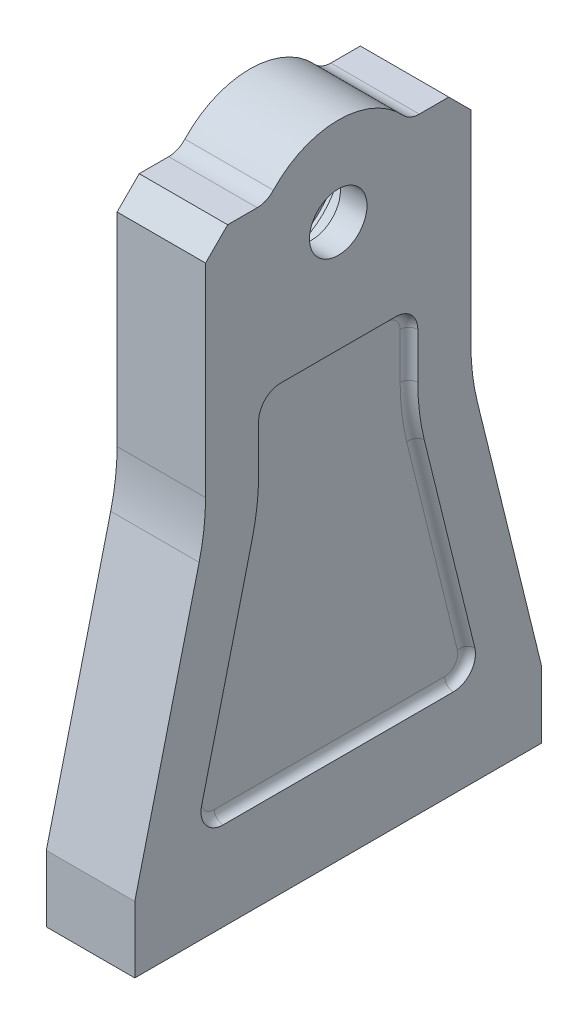
SolidWorks part; units mm, degrees
ref_plane "Front Plane" through (0, 0, 0) normal (0, 0, 1) x (1, 0, 0)
ref_plane "Top Plane" through (0, 0, 0) normal (0, 1, 0) x (1, 0, 0)
ref_plane "Right Plane" through (0, 0, 0) normal (1, 0, 0) x (0, 0, -1)
sketch "Sketch1" plane through (0, 0, 0) normal (1, 0, 0) x (0, 0, -1)
  line L0 (0, 133.7945) -> (0, -11.2055) construction
  line L1 (-46, -11.2055) -> (46, -11.2055)
  line L2 (-46, -11.2055) -> (-46, 3.7945)
  line L3 (-46, 3.7945) -> (-30, 68.7945)
  line L4 (-30, 68.7945) -> (-30, 120.7945)
  line L5 (-25, 125.7945) -> (-18.3303, 125.7945)
  line L6 (25, 125.7945) -> (18.3303, 125.7945)
  line L7 (30, 68.7945) -> (30, 120.7945)
  line L8 (46, 3.7945) -> (30, 68.7945)
  line L9 (46, -11.2055) -> (46, 3.7945)
  line L10 (-30, 120.7945) -> (-25, 125.7945)
  line L11 (30, 120.7945) -> (25, 125.7945)
  circle A0 centre (0, 113.7945) radius 6.5
  arc A1 (14.6642, 127.3945) -> (-14.6642, 127.3945) centre (0, 113.7945) ccw
  arc A2 (-18.3303, 125.7945) -> (-14.6642, 127.3945) centre (-18.3303, 130.7945) ccw
  arc A3 (18.3303, 125.7945) -> (14.6642, 127.3945) centre (18.3303, 130.7945) cw
  point P5 (0, -11.2055)
  point P9 (-30, 125.7945)
  point P13 (30, 125.7945)
  dimension "D7" = 13
  dimension "D8" = 40
  dimension "D9" = 5
  dimension "D1" = 92
  dimension "D2" = 30
  dimension "D3" = 15
  dimension "D4" = 65
  dimension "D5" = 12
  dimension "D6" = 125
extrude "Boss-Extrude1" add sketch "Sketch1" along normal mid plane 20
sketch "Sketch2" plane through (10, 0, 0) normal (1, 0, 0) x (0, 0, -1)
  line L28 (13, 88.7945) -> (-13, 88.7945)
  line L29 (-46, -11.2055) -> (46, -11.2055) construction
  line L30 (-26.031, 8.7945) -> (26.031, 8.7945)
  line L35 (-18, 120.7945) -> (-18, 67.3393)
  line L36 (18, 67.3393) -> (18, 120.7945)
  line L37 (34, 2.3393) -> (18, 67.3393)
  line L38 (34, 0.7945) -> (34, 2.3393)
  line L39 (-34, 0.7945) -> (34, 0.7945)
  line L40 (-34, 2.3393) -> (-34, 0.7945)
  line L41 (-18, 67.3393) -> (-34, 2.3393)
  line L42 (-18, 83.7945) -> (-18, 73.4026)
  line L43 (18, 73.4026) -> (18, 83.7945)
  line L44 (30.8861, 14.9896) -> (19.4493, 61.4517)
  line L48 (-19.4493, 61.4517) -> (-30.8861, 14.9896)
  arc A0 (-26.031, 8.7945) -> (-30.8861, 14.9896) centre (-26.031, 13.7945) cw
  arc A1 (26.031, 8.7945) -> (30.8861, 14.9896) centre (26.031, 13.7945) ccw
  arc A2 (13, 88.7945) -> (18, 83.7945) centre (13, 83.7945) cw
  arc A3 (-13, 88.7945) -> (-18, 83.7945) centre (-13, 83.7945) ccw
  arc A4 (18, 73.4026) -> (19.4493, 61.4517) centre (68, 73.4026) ccw
  arc A5 (-18, 73.4026) -> (-19.4493, 61.4517) centre (-68, 73.4026) cw
  dimension "D4" = 5
  dimension "D5" = 50
  dimension "D2" = 100
  dimension "D3" = 20
  dimension "D1" = 12
extrude "Cut-Extrude1" cut sketch "Sketch2" against normal mid plane 4
fillet "Fillet1" radius 2 12 edges at (8, 38.2206, 25.1677) (8, 67.3834, 18.3636) (8, 78.5986, 18) (8, 87.33, 16.5355) (8, 88.7945, 0) (8, 87.33, -16.5355) (8, 78.5986, -18) (8, 67.3834, -18.3636) (8, 38.2206, -25.1677) (8, 10.7103, -29.9665) (8, 8.7945, 0) (8, 10.7103, 29.9665)
mirror "Mirror4" about plane through (0, 0, 0) normal (1, 0, 0) of "Cut-Extrude1", "Fillet1"
fillet "Fillet2" radius 50 2 edges at (0, 68.7945, 30) (0, 68.7945, -30)
sketch "Sketch3" plane through (0, -11.2055, 0) normal (0, -1, 0) x (1, 0, 0)
  circle A0 centre (0, 30) radius 3
  circle A1 centre (0, -30) radius 3
  dimension "D1" = 6
  dimension "D2" = 60
  dimension "D3" = 30
extrude "Cut-Extrude2" cut sketch "Sketch3" against normal blind 10
sketch "Sketch4" plane through (-10, 0, 0) normal (-1, 0, 0) x (0, 0, 1)
  circle A0 centre (0, 113.7945) radius 15
  dimension "D1" = 30
extrude "Cut-Extrude3" cut sketch "Sketch4" against normal blind 14
chamfer "Chamfer1" distance 1 angle 45 1 edges at (-10, 113.7945, 15)
sketch "Sketch5" plane through (-10, 0, 0) normal (-1, 0, 0) x (0, 0, 1)
  circle A0 centre (0, 113.7945) radius 16 construction
  circle A1 centre (0, 113.7945) radius 16
extrude "Cut-Extrude4" cut sketch "Sketch5" along normal blind 1.5 from offset 6 offset against normal yes
